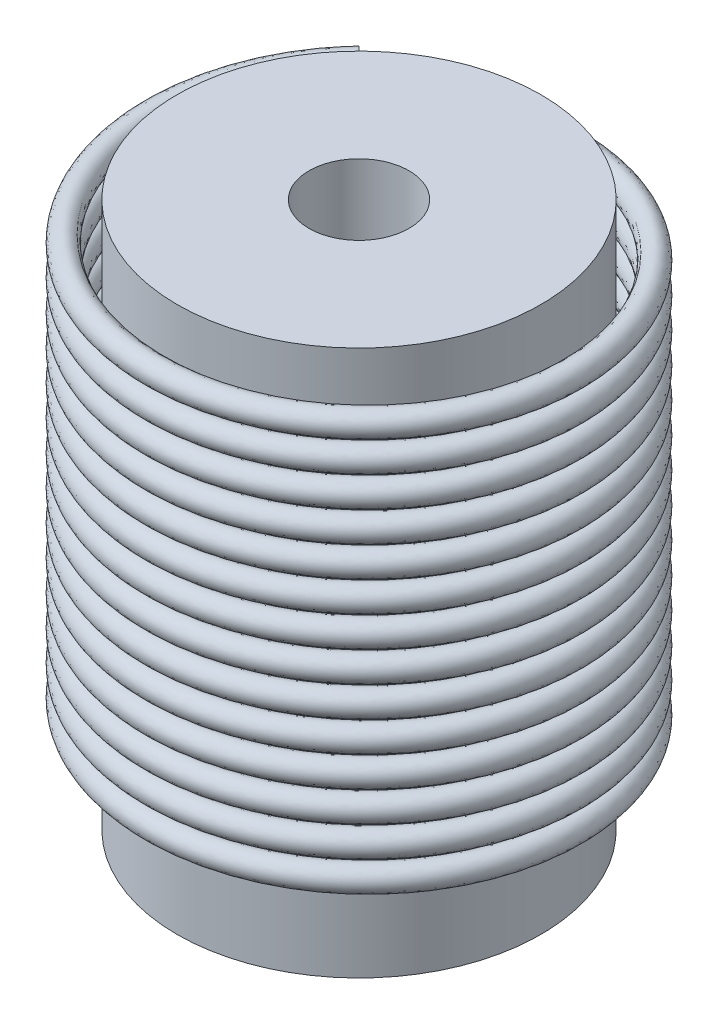
SolidWorks part; units mm, degrees
ref_plane "前视基准面" through (0, 0, 0) normal (0, 0, 1) x (1, 0, 0)
ref_plane "上视基准面" through (0, 0, 0) normal (0, 1, 0) x (1, 0, 0)
ref_plane "右视基准面" through (0, 0, 0) normal (1, 0, 0) x (0, 0, -1)
sketch "草图1" plane through (0, 0, 0) normal (0, 1, 0) x (1, 0, 0)
  circle A0 centre (0, 0) radius 6
extrude "凸台-拉伸2" add sketch "草图1" along normal blind 16 and the other way blind 2
sketch "草图2" plane through (0, 0, 0) normal (0, 1, 0) x (1, 0, 0)
  circle A0 centre (0, 0) radius 6.5
curve "螺旋线/涡状线1" pitch 1 height 15 turns 15
sketch "草图5" plane through (0, 0, 0) normal (0, 0, 1) x (1, 0, 0)
  circle A0 centre (-6.8995, 0.8949) radius 0.4
  spline S0 degree 3 poles (-4.5962, 0) (-3.9984, 0.0207) (-2.5504, 0.0626) (-0.0005, 0.125) (2.5523, 0.1875) (4.7158, 0.25) (6.1616, 0.3125) (6.6692, 0.375) (6.1616, 0.4375) (4.7159, 0.5) (2.5522, 0.5625) (0, 0.625) (-2.5522, 0.6875) (-4.7159, 0.75) (-6.1616, 0.8125) (-6.6692, 0.875) (-6.1616, 0.9375) (-4.7159, 1) (-2.5522, 1.0625) (0, 1.125) (2.5522, 1.1875) (4.7159, 1.25) (6.1616, 1.3125) (6.6692, 1.375) (6.1616, 1.4375) (4.7159, 1.5) (2.5522, 1.5625) (0, 1.625) (-2.5522, 1.6875) (-4.7159, 1.75) (-6.1616, 1.8125) (-6.6692, 1.875) (-6.1616, 1.9375) (-4.7159, 2) (-2.5522, 2.0625) (0, 2.125) (2.5522, 2.1875) (4.7159, 2.25) (6.1616, 2.3125) (6.6692, 2.375) (6.1616, 2.4375) (4.7159, 2.5) (2.5522, 2.5625) (0, 2.625) (-2.5522, 2.6875) (-4.7159, 2.75) (-6.1616, 2.8125) (-6.6692, 2.875) (-6.1616, 2.9375) (-4.7159, 3) (-2.5522, 3.0625) (0, 3.125) (2.5522, 3.1875) (4.7159, 3.25) (6.1616, 3.3125) (6.6692, 3.375) (6.1616, 3.4375) (4.7159, 3.5) (2.5522, 3.5625) (0, 3.625) (-2.5522, 3.6875) (-4.7159, 3.75) (-6.1616, 3.8125) (-6.6692, 3.875) (-6.1616, 3.9375) (-4.7159, 4) (-2.5522, 4.0625) (0, 4.125) (2.5522, 4.1875) (4.7159, 4.25) (6.1616, 4.3125) (6.6692, 4.375) (6.1616, 4.4375) (4.7159, 4.5) (2.5522, 4.5625) (0, 4.625) (-2.5522, 4.6875) (-4.7159, 4.75) (-6.1616, 4.8125) (-6.6692, 4.875) (-6.1616, 4.9375) (-4.7159, 5) (-2.5522, 5.0625) (0, 5.125) (2.5522, 5.1875) (4.7159, 5.25) (6.1616, 5.3125) (6.6692, 5.375) (6.1616, 5.4375) (4.7159, 5.5) (2.5522, 5.5625) (0, 5.625) (-2.5522, 5.6875) (-4.7159, 5.75) (-6.1616, 5.8125) (-6.6692, 5.875) (-6.1616, 5.9375) (-4.7159, 6) (-2.5522, 6.0625) (0, 6.125) (2.5522, 6.1875) (4.7159, 6.25) (6.1616, 6.3125) (6.6692, 6.375) (6.1616, 6.4375) (4.7159, 6.5) (2.5522, 6.5625) (0, 6.625) (-2.5522, 6.6875) (-4.7159, 6.75) (-6.1616, 6.8125) (-6.6692, 6.875) (-6.1616, 6.9375) (-4.7159, 7) (-2.5522, 7.0625) (0, 7.125) (2.5522, 7.1875) (4.7159, 7.25) (6.1616, 7.3125) (6.6692, 7.375) (6.1616, 7.4375) (4.7159, 7.5) (2.5522, 7.5625) (0, 7.625) (-2.5522, 7.6875) (-4.7159, 7.75) (-6.1616, 7.8125) (-6.6692, 7.875) (-6.1616, 7.9375) (-4.7159, 8) (-2.5522, 8.0625) (0, 8.125) (2.5522, 8.1875) (4.7159, 8.25) (6.1616, 8.3125) (6.6692, 8.375) (6.1616, 8.4375) (4.7159, 8.5) (2.5522, 8.5625) (0, 8.625) (-2.5522, 8.6875) (-4.7159, 8.75) (-6.1616, 8.8125) (-6.6692, 8.875) (-6.1616, 8.9375) (-4.7159, 9) (-2.5522, 9.0625) (0, 9.125) (2.5522, 9.1875) (4.7159, 9.25) (6.1616, 9.3125) (6.6692, 9.375) (6.1616, 9.4375) (4.7159, 9.5) (2.5522, 9.5625) (0, 9.625) (-2.5522, 9.6875) (-4.7159, 9.75) (-6.1616, 9.8125) (-6.6692, 9.875) (-6.1616, 9.9375) (-4.7159, 10) (-2.5522, 10.0625) (0, 10.125) (2.5522, 10.1875) (4.7159, 10.25) (6.1616, 10.3125) (6.6692, 10.375) (6.1616, 10.4375) (4.7159, 10.5) (2.5522, 10.5625) (0, 10.625) (-2.5522, 10.6875) (-4.7159, 10.75) (-6.1616, 10.8125) (-6.6692, 10.875) (-6.1616, 10.9375) (-4.7159, 11) (-2.5522, 11.0625) (0, 11.125) (2.5522, 11.1875) (4.7159, 11.25) (6.1616, 11.3125) (6.6692, 11.375) (6.1616, 11.4375) (4.7159, 11.5) (2.5522, 11.5625) (0, 11.625) (-2.5522, 11.6875) (-4.7159, 11.75) (-6.1616, 11.8125) (-6.6692, 11.875) (-6.1616, 11.9375) (-4.7159, 12) (-2.5522, 12.0625) (0, 12.125) (2.5522, 12.1875) (4.7159, 12.25) (6.1616, 12.3125) (6.6692, 12.375) (6.1616, 12.4375) (4.7159, 12.5) (2.5522, 12.5625) (0, 12.625) (-2.5522, 12.6875) (-4.7159, 12.75) (-6.1616, 12.8125) (-6.6692, 12.875) (-6.1616, 12.9375) (-4.7159, 13) (-2.5522, 13.0625) (0, 13.125) (2.5522, 13.1875) (4.7159, 13.25) (6.1616, 13.3125) (6.6692, 13.375) (6.1616, 13.4375) (4.7159, 13.5) (2.5522, 13.5625) (0, 13.625) (-2.5522, 13.6875) (-4.7159, 13.75) (-6.1616, 13.8125) (-6.6692, 13.875) (-6.1616, 13.9375) (-4.7159, 14) (-2.5522, 14.0625) (0, 14.125) (2.5522, 14.1875) (4.7159, 14.25) (6.1616, 14.3125) (6.6692, 14.375) (6.1616, 14.4375) (4.7159, 14.5) (2.5522, 14.5625) (0, 14.625) (-2.5522, 14.6875) (-4.7158, 14.75) (-6.1617, 14.8125) (-6.6688, 14.875) (-6.1633, 14.9374) (-5.194, 14.9793) (-4.5962, 15) knots 0 0 0 0 0.004167 0.008333 0.0125 0.016667 0.020833 0.025 0.029167 0.033333 0.0375 0.041667 0.045833 0.05 0.054167 0.058333 0.0625 0.066667 0.070833 0.075 0.079167 0.083333 0.0875 0.091667 0.095833 0.1 0.104167 0.108333 0.1125 0.116667 0.120833 0.125 0.129167 0.133333 0.1375 0.141667 0.145833 0.15 0.154167 0.158333 0.1625 0.166667 0.170833 0.175 0.179167 0.183333 0.1875 0.191667 0.195833 0.2 0.204167 0.208333 0.2125 0.216667 0.220833 0.225 0.229167 0.233333 0.2375 0.241667 0.245833 0.25 0.254167 0.258333 0.2625 0.266667 0.270833 0.275 0.279167 0.283333 0.2875 0.291667 0.295833 0.3 0.304167 0.308333 0.3125 0.316667 0.320833 0.325 0.329167 0.333333 0.3375 0.341667 0.345833 0.35 0.354167 0.358333 0.3625 0.366667 0.370833 0.375 0.379167 0.383333 0.3875 0.391667 0.395833 0.4 0.404167 0.408333 0.4125 0.416667 0.420833 0.425 0.429167 0.433333 0.4375 0.441667 0.445833 0.45 0.454167 0.458333 0.4625 0.466667 0.470833 0.475 0.479167 0.483333 0.4875 0.491667 0.495833 0.5 0.504167 0.508333 0.5125 0.516667 0.520833 0.525 0.529167 0.533333 0.5375 0.541667 0.545833 0.55 0.554167 0.558333 0.5625 0.566667 0.570833 0.575 0.579167 0.583333 0.5875 0.591667 0.595833 0.6 0.604167 0.608333 0.6125 0.616667 0.620833 0.625 0.629167 0.633333 0.6375 0.641667 0.645833 0.65 0.654167 0.658333 0.6625 0.666667 0.670833 0.675 0.679167 0.683333 0.6875 0.691667 0.695833 0.7 0.704167 0.708333 0.7125 0.716667 0.720833 0.725 0.729167 0.733333 0.7375 0.741667 0.745833 0.75 0.754167 0.758333 0.7625 0.766667 0.770833 0.775 0.779167 0.783333 0.7875 0.791667 0.795833 0.8 0.804167 0.808333 0.8125 0.816667 0.820833 0.825 0.829167 0.833333 0.8375 0.841667 0.845833 0.85 0.854167 0.858333 0.8625 0.866667 0.870833 0.875 0.879167 0.883333 0.8875 0.891667 0.895833 0.9 0.904167 0.908333 0.9125 0.916667 0.920833 0.925 0.929167 0.933333 0.9375 0.941667 0.945833 0.95 0.954167 0.958333 0.9625 0.966667 0.970833 0.975 0.979167 0.983333 0.9875 0.991667 0.995833 1 1 1 1 construction
sweep "扫描2" add profiles "草图5" path "螺旋线/涡状线1"
ref_plane "基准面1" through (0, 16, 0) normal (0, 1, 0) x (1, 0, 0)
hole_wizard "M4 螺纹孔1" positions "草图7" profile "草图6" tap size "M4" standard "GB"
sketch "草图7" plane through (0, 16, 0) normal (0, 1, 0) x (1, 0, 0)
  point P0 (0, 0)
sketch "草图6" plane through (0, 16, 0) normal (1, 0, 0) x (0, 0, 1)
  line L0 (0, 0) -> (0, 12.4914)
  line L1 (0, 12.4914) -> (1.65, 11.5)
  line L2 (1.65, 11.5) -> (1.65, 0)
  line L5 (1.65, 0) -> (0, 0)
  line L10 (0, 12.4914) -> (-1.65, 11.5) construction
  line L11 (0, -6.35) -> (0, 107.95) construction
  dimension "螺纹孔钻头直径" = 3.3
  dimension "螺纹孔钻头深度" = 11.5
  dimension "导头角度" = 118
cosmetic thread "孔螺蚊线1" parameters "D1"=8, "D2"=4
